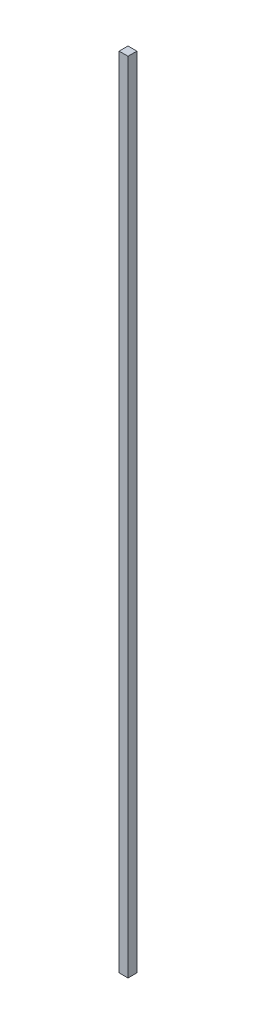
SolidWorks part; units mm, degrees
ref_plane "Front Plane" through (0, 0, 0) normal (0, 0, 1) x (1, 0, 0)
ref_plane "Top Plane" through (0, 0, 0) normal (0, 1, 0) x (1, 0, 0)
ref_plane "Right Plane" through (0, 0, 0) normal (1, 0, 0) x (0, 0, -1)
sketch "Sketch1" plane through (0, 0, 0) normal (0, 1, 0) x (1, 0, 0)
  line L1 (0, 0) -> (25.4, 0)
  line L2 (0, 0) -> (0, 25.4)
  line L3 (0, 25.4) -> (25.4, 25.4)
  line L4 (25.4, 0) -> (25.4, 25.4)
  dimension "D1" = 25.4
  dimension "D2" = 25.4
extrude "Boss-Extrude1" add sketch "Sketch1" along normal blind 2286
